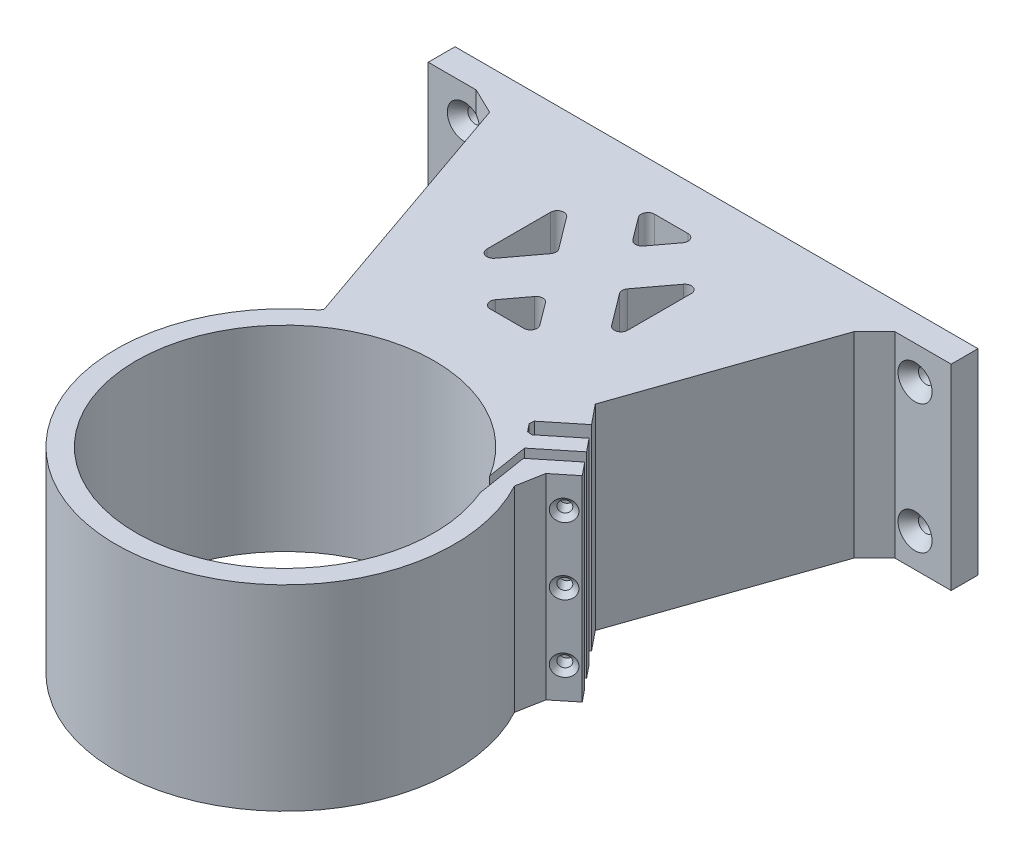
SolidWorks part; units mm, degrees
ref_plane "Front Plane" through (0, 0, 0) normal (0, 0, 1) x (1, 0, 0)
ref_plane "Top Plane" through (0, 0, 0) normal (0, 1, 0) x (1, 0, 0)
ref_plane "Right Plane" through (0, 0, 0) normal (1, 0, 0) x (0, 0, -1)
sketch "Sketch1" plane through (0, 0, 0) normal (0, 1, 0) x (1, 0, 0)
  line L0 (-27.5, 42.296) -> (-27.5, 82.296)
  line L5 (-27.5, 82.296) -> (-22.5, 82.296)
  line L6 (-22.5, 82.296) -> (-22.5, 72.296) construction
  line L7 (-22.5, 72.296) -> (22.5, 72.296) construction
  line L8 (22.5, 72.296) -> (22.5, 82.296) construction
  line L10 (32.5, 60.6712) -> (32.5, 38.6856) construction
  line L11 (36.0591, 35.3916) -> (38.0164, 23.0338)
  line L12 (38.5317, 32.5655) -> (40.952, 17.2839)
  line L14 (36.0591, 35.3916) -> (46.2731, 43.6628)
  line L15 (38.5317, 32.5655) -> (48.6345, 40.7467)
  line L16 (48.6345, 40.7467) -> (51.7812, 36.861)
  line L17 (51.7812, 36.861) -> (41.5671, 28.5898)
  line L18 (46.2731, 43.6628) -> (43.1265, 47.5485)
  line L19 (43.1265, 47.5485) -> (32.9125, 39.2774)
  line L20 (32.9125, 39.2774) -> (29.7659, 43.1631)
  line L21 (29.7659, 43.1631) -> (39.9799, 51.4343)
  line L22 (39.9799, 51.4343) -> (32.5, 60.6712)
  line L23 (22.5, 82.296) -> (32.5, 82.296)
  line L24 (32.5, 82.296) -> (32.5, 60.6712)
  line L30 (0, 44.45) -> (0, 72.296) construction
  line L31 (-22.5, 82.296) -> (22.5, 82.296)
  arc A1 (38.0164, 23.0338) -> (40.952, 17.2839) centre (0, 0) ccw
  arc A2 (36.0591, 35.3916) -> (32.5, 38.6856) centre (0, 0) ccw construction
  arc A3 (41.5671, 28.5898) -> (38.5317, 32.5655) centre (0, 0) ccw construction
  arc A4 (-27.5, 42.296) -> (41.5671, 28.5898) centre (0, 0) ccw
  point P9 (0, 72.296)
  point P13 (0, 70.296)
  point P25 (34.2196, 16.7519)
  point P26 (37.8268, 23.3439)
  dimension "D2" = 6
  dimension "D7" = 44.45
  dimension "D3" = 45
  dimension "D4" = 5
  dimension "D5" = 5
  dimension "D6" = 2
  dimension "D8" = 2
  dimension "D9" = 3
  dimension "D10" = 120
  dimension "D11" = 13
  dimension "D12" = 5
  dimension "D13" = 5
  dimension "D14" = 10
  dimension "D15" = 30
  dimension "D16" = 10
  dimension "D17" = 9
extrude "Boss-Extrude1" add sketch "Sketch1" along normal mid plane 58.5
chamfer "Chamfer1" distance 5 angle 45 1 edges at (41.5671, 0, -28.5898) first distance on face at (-1.3933, 0, 7.0211)
fillet "Fillet1" radius 10 1 edges at (-27.5, 0, -42.296)
chamfer "Chamfer2" distance 1 angle 45 2 edges at (29.7659, 0, -43.1631) (32.9125, 0, -39.2774)
hole_wizard "CSK for M3 Flat Head Machine Screw1" positions "Sketch2" profile "Sketch3" countersink size "M3" standard "ANSI Metric"
sketch "Sketch2" plane through (2.4799, 0, 3.0624) normal (0.6293, 0, 0.7771) x (0.7771, 0, -0.6293)
  line L0 (55.7375, 29.25) -> (63.4389, 29.25) construction
  point P0 (59.5882, 20)
  point P2 (59.5882, 0)
  point P4 (59.5882, -20)
  point P16 (59.5882, 29.25)
  dimension "D1" = 20
  dimension "D2" = 20
sketch "Sketch3" plane through (48.7886, 20, -34.4377) normal (0, 1, 0) x (0.7771, 0, -0.6293)
  line L0 (0, 0) -> (0, 16.0215)
  line L1 (0, 16.0215) -> (1.7, 15)
  line L2 (1.7, 15) -> (1.7, 1.45)
  line L3 (1.7, 1.45) -> (3.15, 0)
  line L5 (3.15, 0) -> (0, 0)
  line L6 (-1.7, 1.45) -> (-3.15, 0) construction
  line L10 (0, 16.0215) -> (-1.7, 15) construction
  line L11 (0, -6.35) -> (0, 107.95) construction
  dimension "Hole Dia." = 3.4
  dimension "Hole Depth" = 15
  dimension "Near C'Sink Dia." = 6.3
  dimension "Near C'Sink Angle" = 90
  dimension "Drill Angle" = 118
sketch "Sketch4" plane through (0, 29.25, 0) normal (0, 1, 0) x (1, 0, 0)
  line L0 (-27.473, 34.9433) -> (-60, 128.7)
  line L1 (-60, 128.7) -> (60, 128.7)
  line L2 (60, 128.7) -> (27.473, 34.9433)
  line L3 (60, 128.7) -> (78, 128.7)
  line L4 (78, 128.7) -> (78, 120.7)
  line L5 (78, 120.7) -> (57.2246, 120.7)
  line L6 (-60, 128.7) -> (-78, 128.7)
  line L7 (-78, 128.7) -> (-78, 120.7)
  line L8 (-78, 120.7) -> (-57.2246, 120.7)
  arc A0 (38.0164, 23.0338) -> (40.952, 17.2839) centre (0, 0) ccw construction
  arc A1 (-27.473, 34.9433) -> (27.473, 34.9433) centre (0, 0) cw
  point P8 (0, 128.7)
  point P16 (0, 0)
  line M8 (39.9799, 51.4343) -> (32.5, 60.6712)
  line M9 (32.5, 60.6712) -> (32.5, 82.296)
  line M10 (32.5, 82.296) -> (-27.5, 82.296)
  line M11 (-27.5, 82.296) -> (-27.5, 47.4126)
  arc M12 (-27.5, 47.4126) -> (-31.2965, 39.5693) centre (-37.5, 47.4126) cw
  dimension "D1" = 128.7
  dimension "D2" = 120
  dimension "D3" = 8
  dimension "D4" = 18
extrude "Boss-Extrude2" add sketch "Sketch4" against normal up to surface (58.5 mm away) contours L2 L1 L0 M12 M11 M10 M9 M8 | L7 L8 L0 L6 | L5 L4 L3 L2 region at (-68.2896, 29.25, -124.6046) region at (-1.1519, 29.25, -102.8434) region at (68.2896, 29.25, -124.6046) up to face at (24.2143, -29.25, -37.0477)
sketch "Sketch5" plane through (0, -29.25, 0) normal (0, -1, 0) x (1, 0, 0)
  line L13 (15, -110.7) -> (-15, -70.7) construction
  line L14 (9, -115.2) -> (-21, -75.2)
  line L15 (21, -106.2) -> (-9, -66.2)
  line L16 (-15, -110.7) -> (15, -70.7) construction
  line L17 (-21, -106.2) -> (9, -66.2)
  line L18 (-9, -115.2) -> (21, -75.2)
  line L19 (-9, -66.2) -> (9, -66.2)
  line L20 (21, -75.2) -> (21, -106.2)
  line L21 (9, -115.2) -> (-9, -115.2)
  line L22 (-21, -75.2) -> (-21, -106.2)
  line L25 (-57.2246, -120.7) -> (-78, -120.7) construction
  arc A0 (9, -115.2) -> (21, -106.2) centre (15, -110.7) ccw
  arc A1 (-9, -66.2) -> (-21, -75.2) centre (-15, -70.7) ccw
  arc A2 (-21, -106.2) -> (-9, -115.2) centre (-15, -110.7) ccw
  arc A3 (21, -75.2) -> (9, -66.2) centre (15, -70.7) ccw
  point P2 (0, -90.7)
  point P8 (0, -90.7)
  point P18 (-21, -93.7082)
  point P21 (-21, -77.2604)
  point P22 (-21, -108.2604)
  point P25 (0, -85.7649)
  dimension "D1" = 15
  dimension "D2" = 20
  dimension "D3" = 30
  dimension "D4" = 15
  dimension "D5" = 30
extrude "Cut-Extrude1" cut sketch "Sketch5" against normal through all contours L21 L14 L18 | L14 L22 L17 | L19 L15 L17 | L20 L18 L15 region at (0, -29.25, -111.2) region at (17.125, -29.25, -90.7) region at (-17.125, -29.25, -90.7) region at (0, -29.25, -70.2)
fillet "Fillet2" radius 2 12 edges at (0, 0, -103.2) (-9, 0, -115.2) (9, 0, -115.2) (21, 0, -106.2) (21, 0, -75.2) (9.375, 0, -90.7) (0, 0, -78.2) (9, 0, -66.2) (-9, 0, -66.2) (-21, 0, -106.2) (-9.375, 0, -90.7) (-21, 0, -75.2)
hole_wizard "CSK for #8 Flat Head Machine Screw1" positions "Sketch6" profile "Sketch7" countersink size "#8" standard "ANSI Inch" end condition through all
sketch "Sketch6" plane through (0, 0, -120.7) normal (0, 0, 1) x (1, 0, 0)
  line L0 (-57.2246, -29.25) -> (-57.2246, 29.25) construction
  line L1 (-78, 29.25) -> (-57.2246, 29.25) construction
  line L2 (-57.2246, -29.25) -> (-78, -29.25) construction
  line L4 (57.2246, -29.25) -> (57.2246, 29.25) construction
  point P0 (-67.2246, 19.25)
  point P2 (-67.2246, -19.25)
  point P4 (67.2246, 19.25)
  point P6 (67.2246, -19.25)
  point P9 (0, 0)
  point P10 (0, 0)
  point P11 (0, 0)
  point P12 (0, 0)
  point P15 (0, 0)
  dimension "D1" = 10
  dimension "D2" = 10
  dimension "D3" = 10
  dimension "D4" = 10
sketch "Sketch7" plane through (-67.2246, 19.25, -120.7) normal (1, 0, 0) x (0, -1, 0)
  line L0 (0, 0) -> (0, 8)
  line L1 (0, 8) -> (2.2479, 8)
  line L2 (2.2479, 8) -> (2.2479, 3.2645)
  line L3 (2.2479, 3.2645) -> (5.0857, 0)
  line L5 (5.0857, 0) -> (0, 0)
  line L6 (-2.2479, 3.2645) -> (-5.0857, 0) construction
  line L11 (0, -6.35) -> (0, 107.95) construction
  dimension "Thru Hole Dia." = 4.4958
  dimension "Thru Hole Depth" = 8
  dimension "Near C'Sink Dia." = 10.1714
  dimension "Near C'Sink Angle" = 82
chamfer "Chamfer3" distance 4 angle 45 2 edges at (57.2246, 0, -120.7) (-57.2246, 0, -120.7) first distance on face at (72.3103, 19.25, -120.7) first distance on face at (-43.4372, 0, -80.9589)
